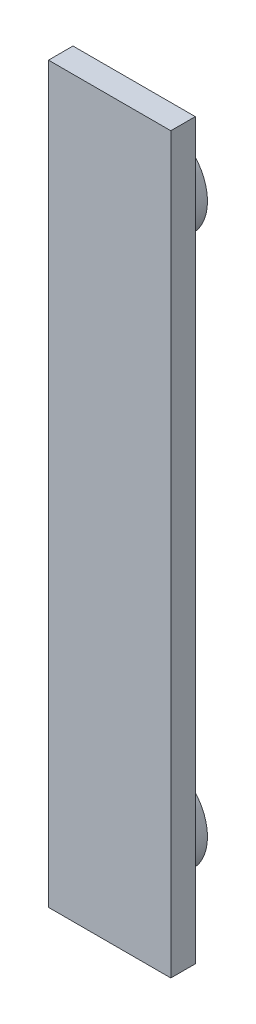
SolidWorks part; units mm, degrees
ref_plane "Front Plane" through (0, 0, 0) normal (0, 0, 1) x (1, 0, 0)
ref_plane "Top Plane" through (0, 0, 0) normal (0, 1, 0) x (1, 0, 0)
ref_plane "Right Plane" through (0, 0, 0) normal (1, 0, 0) x (0, 0, -1)
sketch "Sketch1" plane through (0, 0, 0) normal (0, 0, 1) x (1, 0, 0)
  line L1 (5, -30) -> (-5, -30)
  line L2 (5, -30) -> (5, 30)
  line L3 (5, 30) -> (-5, 30)
  line L4 (-5, -30) -> (-5, 30)
  line L5 (5, -30) -> (-5, 30) construction
  line L6 (5, 30) -> (-5, -30) construction
  circle A0 centre (0, 22.5) radius 4
  circle A1 centre (0, -22.5) radius 4
  point P0 (0, 0)
  point P8 (0, 0)
  dimension "D3" = 8
  dimension "D1" = 10
  dimension "D2" = 60
  dimension "D4" = 22.5
  dimension "D5" = 22.5
extrude "Boss-Extrude1" add sketch "Sketch1" along normal blind 2 contours A0 | L4 L1 L2 L3 A1 A0 | A1 region at (0, 0, 0) region at (0, 22.5, 0) region at (0, -22.5, 0)
extrude "Boss-Extrude2" add sketch "Sketch1<3>" against normal blind 2 contours A0 | A1 region at (0, 22.5, 0) region at (0, -22.5, 0)
sketch "Sketch1<3>" plane through (0, 0, 0) normal (0, 0, 1) x (1, 0, 0) same geometry as "Sketch1"
